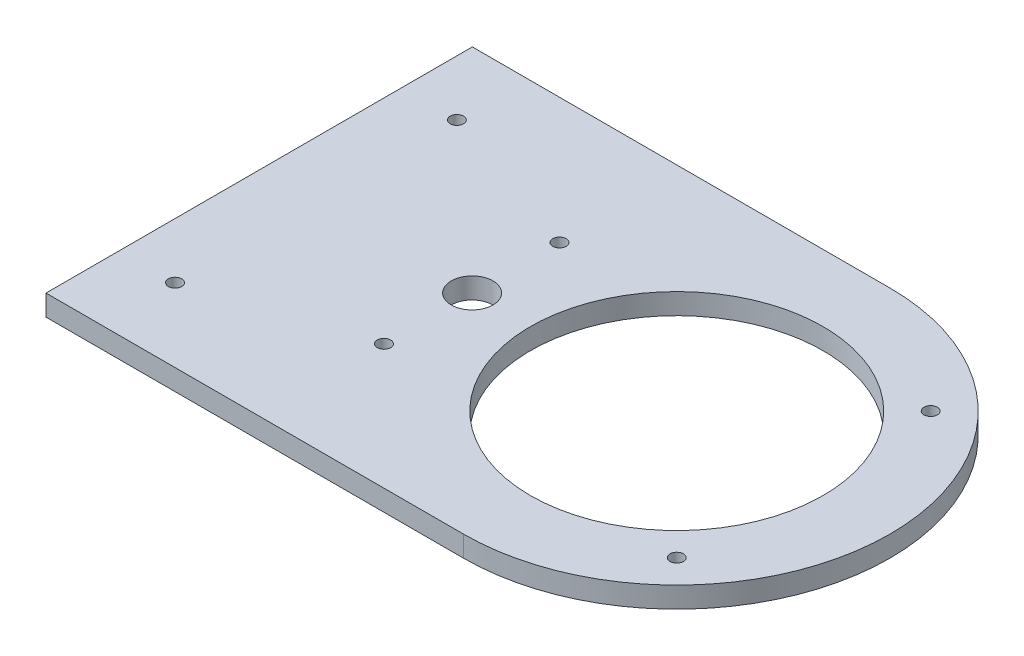
SolidWorks part; units mm, degrees
ref_plane "Front Plane" through (0, 0, 0) normal (0, 0, 1) x (1, 0, 0)
ref_plane "Top Plane" through (0, 0, 0) normal (0, 1, 0) x (1, 0, 0)
ref_plane "Right Plane" through (0, 0, 0) normal (1, 0, 0) x (0, 0, -1)
sketch "Sketch1" plane through (0, 0, 0) normal (0, 1, 0) x (1, 0, 0)
  line L1 (-100, -51.05) -> (78, -51.05)
  line L2 (-100, -51.05) -> (-100, 51.05)
  line L3 (-100, 51.05) -> (78, 51.05)
  line L4 (78, -51.05) -> (78, 51.05)
  circle A0 centre (0, 0) radius 35.05
  circle A1 centre (-49, 0) radius 5
  dimension "D1" = 70.1
  dimension "D3" = 10
  dimension "D2" = 49
  dimension "D4" = 51.05
  dimension "D5" = 100
  dimension "D6" = 102.1
  dimension "D7" = 78
extrude "Boss-Extrude1" add sketch "Sketch1" along normal blind 5
sketch "Sketch2" plane through (0, 0, 0) normal (0, 1, 0) x (1, 0, 0)
  line L0 (0, 0) -> (0, 43) construction
  line L1 (0, 0) -> (30.4056, 30.4056) construction
  circle A1 centre (30.4056, 30.4056) radius 1.25
  circle A2 centre (30.4056, -30.4056) radius 1.25
  circle A3 centre (0, 0) radius 37 construction
  circle A4 centre (0, 0) radius 43 construction
  circle A7 centre (-30.4056, 30.4056) radius 1.25
  circle A8 centre (-30.4056, -30.4056) radius 1.25
  point P17 (0, 0)
  dimension "D1" = 74
  dimension "D3" = 2.5
  dimension "D2" = 45
  dimension "D4" = 6
  dimension "D5" = 4
hole_wizard "CSK for M3 Countersunk Flat Head Screw1" positions "Sketch9" profile "Sketch10" countersink size "M3" standard "ISO" end condition through all
sketch "Sketch9" plane through (0, 0, 0) normal (0, -1, 0) x (-1, 0, 0)
  point P3 (-30.4056, -30.4056)
  point P6 (-30.4056, 30.4056)
sketch "Sketch10" plane through (30.4056, 0, 30.4056) normal (1, 0, 0) x (0, 0, -1)
  line L0 (0, 0) -> (0, 5)
  line L1 (0, 5) -> (1.6, 5)
  line L2 (1.6, 5) -> (1.6, 1.55)
  line L3 (1.6, 1.55) -> (3.15, 0)
  line L5 (3.15, 0) -> (0, 0)
  line L6 (-1.6, 1.55) -> (-3.15, 0) construction
  line L11 (0, -6.35) -> (0, 107.95) construction
  dimension "Thru Hole Dia." = 3.2
  dimension "Thru Hole Depth" = 5
  dimension "Near C'Sink Dia." = 6.3
  dimension "Near C'Sink Angle" = 90
sketch "Sketch12" plane through (0, 5, 0) normal (0, 1, 0) x (1, 0, 0)
  line L0 (78, 51.05) -> (-100, 51.05) construction
  line L1 (0, 51.05) -> (78, 51.05)
  line L2 (78, 51.05) -> (78, -51.05)
  line L3 (78, -51.05) -> (0, -51.05)
  arc A0 (0, -51.05) -> (0, 51.05) centre (0, 0) ccw
extrude "Cut-Extrude2" cut sketch "Sketch12" against normal through all
sketch "Sketch13" plane through (0, 0, 0) normal (0, 1, 0) x (1, 0, 0)
  circle A0 centre (-49, -21.11) radius 1.6
  circle A1 centre (-49, 20.91) radius 1.6
  dimension "D1" = 3.2
  dimension "D2" = 49
  dimension "D3" = 21.11
  dimension "D4" = 42.02
hole_wizard "CSK for M3 Countersunk Flat Head Screw2" positions "Sketch14" profile "Sketch16" countersink size "M3" standard "ISO" end condition through all
sketch "Sketch14" plane through (0, 0, 0) normal (0, -1, 0) x (-1, 0, 0)
  point P0 (49, 20.91)
  point P3 (49, -21.11)
sketch "Sketch16" plane through (-49, 0, -20.91) normal (1, 0, 0) x (0, 0, -1)
  line L0 (0, 0) -> (0, 5)
  line L1 (0, 5) -> (1.6, 5)
  line L2 (1.6, 5) -> (1.6, 1.55)
  line L3 (1.6, 1.55) -> (3.15, 0)
  line L5 (3.15, 0) -> (0, 0)
  line L6 (-1.6, 1.55) -> (-3.15, 0) construction
  line L11 (0, -6.35) -> (0, 107.95) construction
  dimension "Thru Hole Dia." = 3.2
  dimension "Thru Hole Depth" = 5
  dimension "Near C'Sink Dia." = 6.3
  dimension "Near C'Sink Angle" = 90
sketch "Sketch17" plane through (0, 0, 0) normal (0, -1, 0) x (-1, 0, 0)
  line L0 (0, 51.05) -> (100, 51.05) construction
  line L1 (100, -51.05) -> (0, -51.05) construction
  line L2 (100, 51.05) -> (100, -51.05) construction
  circle A0 centre (86.7, 34.05) radius 1.85
  circle A1 centre (86.7, -33.45) radius 1.85
  circle A4 centre (49, 0) radius 5 construction
  circle A5 centre (49, 0) radius 5 construction
  dimension "D5" = 3.7
  dimension "D1" = 17
  dimension "D2" = 17.6
  dimension "D3" = 13.3
  dimension "D4" = 13.3
hole_wizard "CSK for M3 Countersunk Flat Head Screw3" positions "Sketch18" profile "Sketch19" countersink size "M3" standard "ISO" end condition through all
sketch "Sketch18" plane through (0, 0, 0) normal (0, -1, 0) x (-1, 0, 0)
  point P3 (86.7, 34.05)
  point P6 (86.7, -33.45)
sketch "Sketch19" plane through (-86.7, 0, -34.05) normal (1, 0, 0) x (0, 0, -1)
  line L0 (0, 0) -> (0, 5)
  line L1 (0, 5) -> (1.6, 5)
  line L2 (1.6, 5) -> (1.6, 1.55)
  line L3 (1.6, 1.55) -> (3.15, 0)
  line L5 (3.15, 0) -> (0, 0)
  line L6 (-1.6, 1.55) -> (-3.15, 0) construction
  line L11 (0, -6.35) -> (0, 107.95) construction
  dimension "Thru Hole Dia." = 3.2
  dimension "Thru Hole Depth" = 5
  dimension "Near C'Sink Dia." = 6.3
  dimension "Near C'Sink Angle" = 90
equation "\"D4@Sketch1\"=\"D1@Sketch1\"/2+16mm"
equation "\"D6@Sketch1\"=\"D4@Sketch1\"*2"
equation "\"D3@Sketch17\"=\"D4@Sketch17\""
